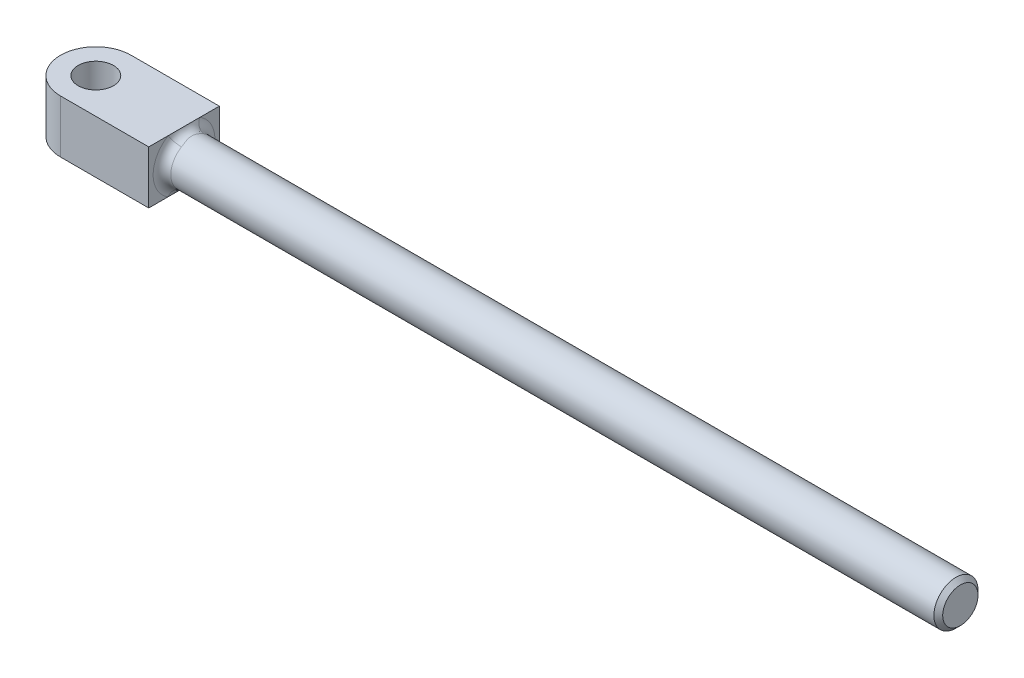
SolidWorks part; units mm, degrees
ref_plane "Front Plane" through (0, 0, 0) normal (0, 0, 1) x (1, 0, 0)
ref_plane "Top Plane" through (0, 0, 0) normal (0, 1, 0) x (1, 0, 0)
ref_plane "Right Plane" through (0, 0, 0) normal (1, 0, 0) x (0, 0, -1)
sketch "Sketch1" plane through (0, 0, 0) normal (1, 0, 0) x (0, 0, -1)
  circle A0 centre (0, 0) radius 2.5
  dimension "D1" = 5
extrude "Boss-Extrude1" add sketch "Sketch1" along normal mid plane 88
cosmetic thread "Cosmetic Thread1" parameters "D1"=14, "D2"=4.11
sketch "Sketch2" plane through (0, 0, 0) normal (0, 1, 0) x (1, 0, 0)
  line L0 (-44, 2.5) -> (-44, -2.5) construction
  line L1 (-44, 4) -> (-54, 4)
  line L2 (-44, 4) -> (-44, -4)
  line L3 (-44, -4) -> (-54, -4)
  line L5 (0, 0) -> (-54, 0) construction
  arc A0 (-54, 4) -> (-54, -4) centre (-54, 0) ccw
  circle A1 centre (-54, 0) radius 2
  point P11 (-44, 0)
  dimension "D3" = 4
  dimension "D1" = 10
  dimension "D2" = 8
extrude "Boss-Extrude2" add sketch "Sketch2" along normal mid plane 6
fillet "Fillet1" radius 1 1 edges at (-44, 0, -2.5)
chamfer "Chamfer1" distance 0.5 angle 45 1 edges at (44, 0, -2.5)
